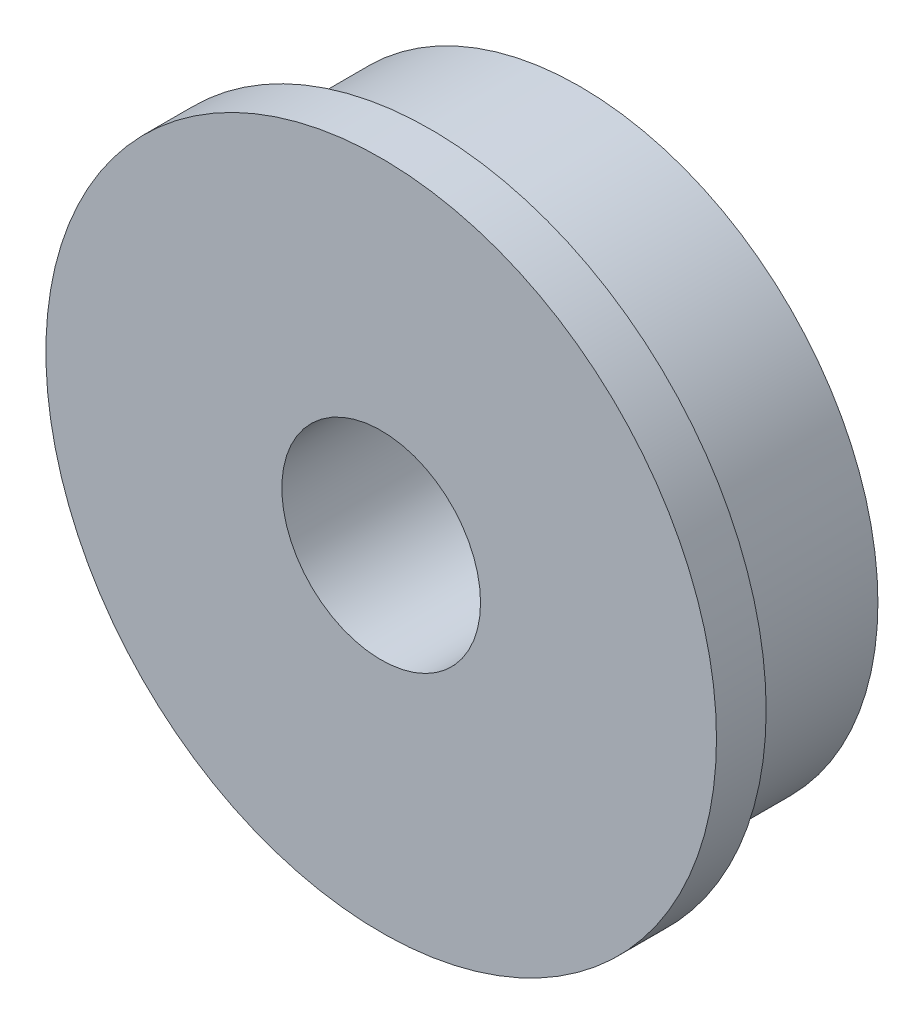
SolidWorks part; units mm, degrees
material "Хромистая нержавеющая сталь"
ref_plane "Front Plane" through (0, 0, 0) normal (0, 0, 1) x (1, 0, 0)
ref_plane "Top Plane" through (0, 0, 0) normal (0, 1, 0) x (1, 0, 0)
ref_plane "Right Plane" through (0, 0, 0) normal (1, 0, 0) x (0, 0, -1)
sketch "Sketch1" plane through (0, 0, 0) normal (0, 0, 1) x (1, 0, 0)
  circle A0 centre (0, 0) radius 6
  circle A1 centre (0, 0) radius 2
  dimension "D1" = 12
  dimension "D2" = 4
extrude "Boss-Extrude1" add sketch "Sketch1" along normal blind 3
sketch "Sketch2" plane through (0, 0, 3) normal (0, 0, 1) x (1, 0, 0)
  circle A0 centre (0, 0) radius 6.75
  circle A1 centre (0, 0) radius 2
  dimension "D1" = 13.5
extrude "Boss-Extrude2" add sketch "Sketch2" along normal blind 1
fillet "Fillet1" radius 0.1 1 edges at (6, 0, 3) second distance 0.01 first distance on face at (6, 0, 3)
